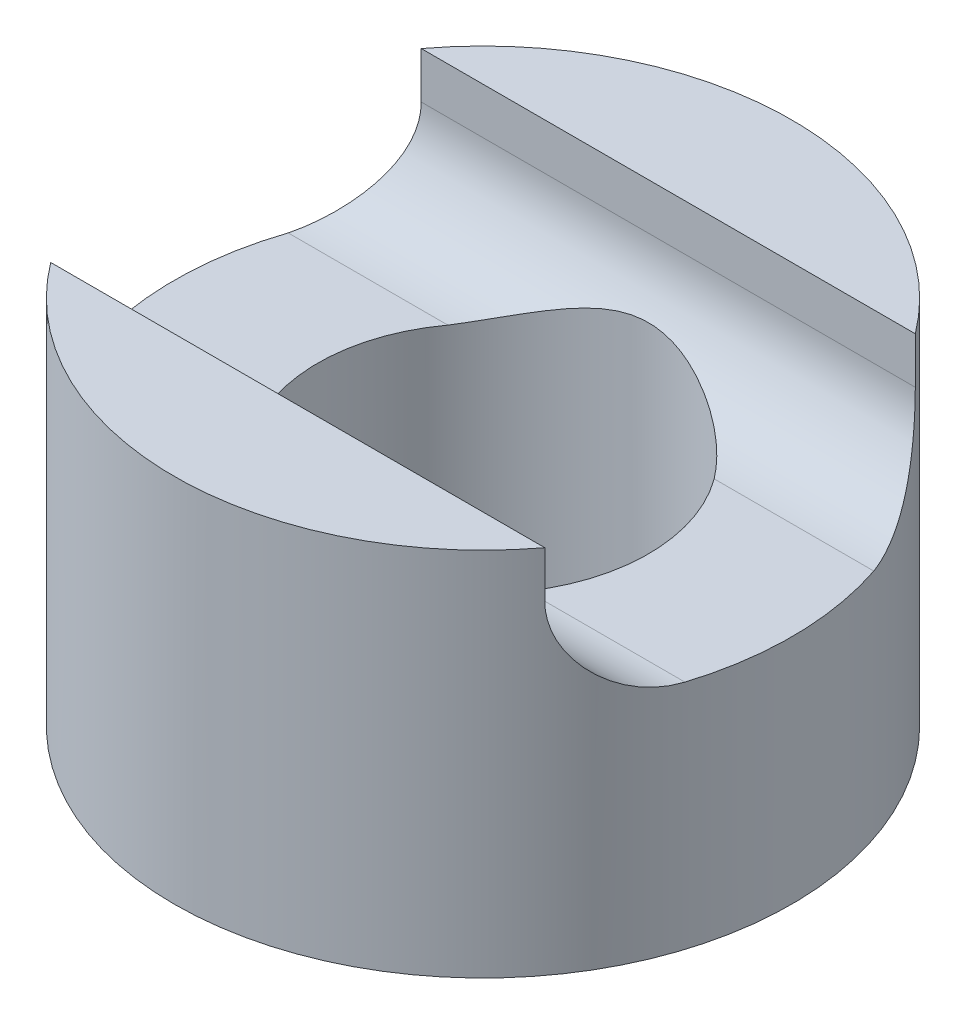
SolidWorks part; units mm, degrees
ref_plane "Front Plane" through (0, 0, 0) normal (0, 0, 1) x (1, 0, 0)
ref_plane "Top Plane" through (0, 0, 0) normal (0, 1, 0) x (1, 0, 0)
ref_plane "Right Plane" through (0, 0, 0) normal (1, 0, 0) x (0, 0, -1)
sketch "Sketch1" plane through (0, 0, 0) normal (0, 1, 0) x (1, 0, 0)
  circle A0 centre (0, 0) radius 4.25
  circle A1 centre (0, 0) radius 7.9375
  dimension "D1" = 8.5
  dimension "D2" = 15.875
extrude "Boss-Extrude1" add sketch "Sketch1" along normal blind 9.525
sketch "Sketch2" plane through (0, 0, 0) normal (1, 0, 0) x (0, 0, -1)
  line L0 (7.9375, 9.525) -> (-7.9375, 9.525) construction
  line L1 (-4.7625, 9.525) -> (4.7625, 9.525)
  line L2 (-4.7625, 9.525) -> (-4.7625, 8.3344)
  line L3 (-2.3812, 5.9531) -> (2.5194, 5.9531)
  line L4 (4.7625, 9.525) -> (4.7625, 8.3344)
  arc A0 (-4.7625, 8.3344) -> (-2.3812, 5.9531) centre (-2.3812, 8.3344) ccw
  arc A1 (4.7625, 8.3344) -> (2.5194, 5.9531) centre (2.377, 8.3344) cw
  point P14 (-2.79, 7.1437)
  point P15 (0, 0)
  point P16 (0, 0)
  dimension "D4" = 2.3855
  dimension "D1" = 9.525
  dimension "D2" = 4.9007
  dimension "D3" = 3.5719
extrude "Cut-Extrude1" cut sketch "Sketch2" against normal through all and the other way through all
